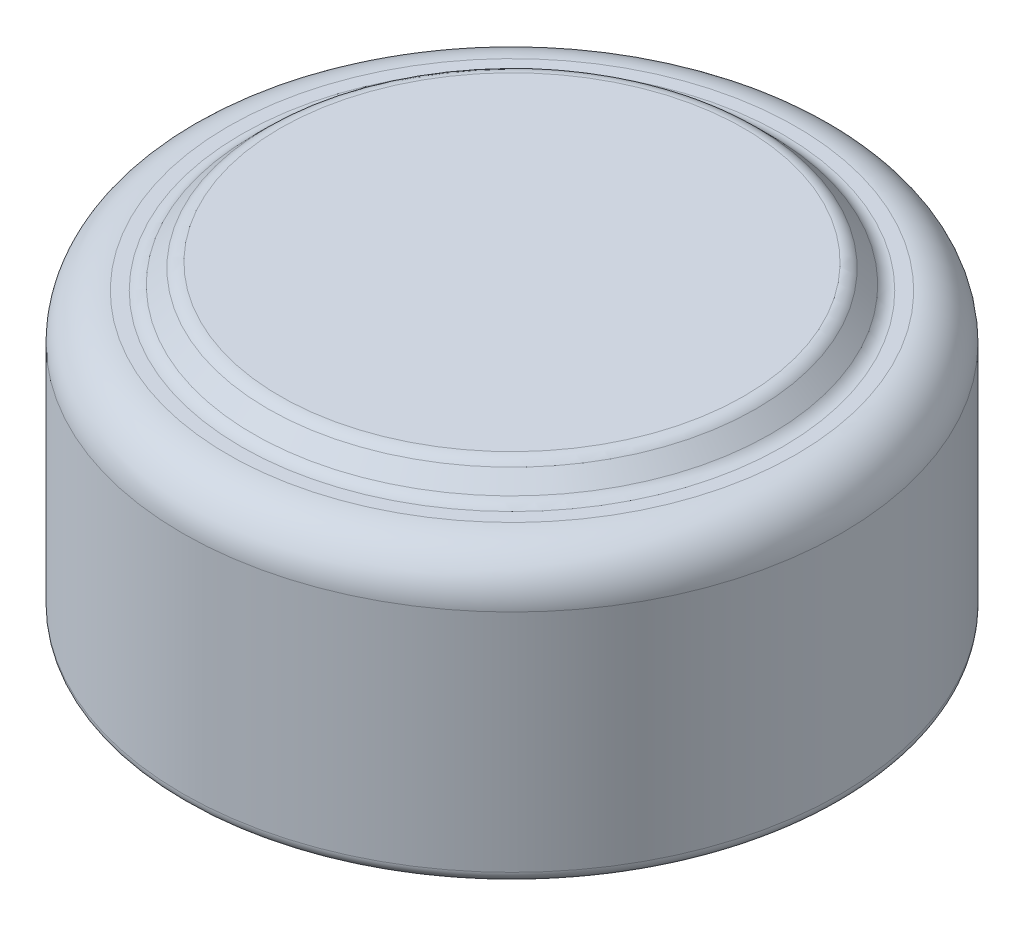
SolidWorks part; units mm, degrees
ref_plane "Front Plane" through (0, 0, 0) normal (0, 0, 1) x (1, 0, 0)
ref_plane "Top Plane" through (0, 0, 0) normal (0, 1, 0) x (1, 0, 0)
ref_plane "Right Plane" through (0, 0, 0) normal (1, 0, 0) x (0, 0, -1)
sketch "Sketch1" plane through (0, 0, 0) normal (0, 0, 1) x (1, 0, 0)
  line L0 (0, 0) -> (-2.8, 0)
  line L1 (-2.9, 0.1) -> (-2.9, 2.084)
  line L2 (-2.0419, 2.7) -> (0, 2.7)
  line L3 (0, 2.7) -> (0, 0)
  line L4 (-2.2761, 2.5279) -> (-2.1479, 2.6561)
  line L7 (-2.3821, 2.484) -> (-2.5, 2.484)
  arc A0 (-2.9, 2.084) -> (-2.5, 2.484) centre (-2.5, 2.084) cw
  arc A1 (-2.0419, 2.7) -> (-2.1479, 2.6561) centre (-2.0419, 2.55) ccw
  arc A2 (-2.3821, 2.484) -> (-2.2761, 2.5279) centre (-2.3821, 2.634) ccw
  arc A3 (-2.8, 0) -> (-2.9, 0.1) centre (-2.8, 0.1) cw
  point P9 (-2.9, 2.484)
  point P13 (-2.32, 2.484)
  point P17 (-2.9, 0)
  point P18 (-2.32, 2.484)
  point P20 (-2.32, 2.484)
  dimension "D6" = 0.4
  dimension "D7" = 0.15
  dimension "D8" = 0.1
  dimension "D1" = 2.9
  dimension "D2" = 2.7
  dimension "D3" = 2.32
  dimension "D4" = 2.484
  dimension "D5" = 45
revolve "Revolve1" add sketch "Sketch1" angle 360 about L3
sketch "Sketch2" plane through (0, 0, 0) normal (0, -1, 0) x (1, 0, 0)
  line L0 (0.25, 0.25) -> (1.4, 0.25)
  line L1 (-0.25, 1.4) -> (0.25, 1.4)
  line L2 (-0.25, 1.4) -> (-0.25, 0.25)
  line L3 (-0.25, -1.4) -> (0.25, -1.4)
  line L4 (0.25, 1.4) -> (0.25, 0.25)
  line L5 (-1.4, 0.25) -> (-0.25, 0.25)
  line L6 (-1.4, 0.25) -> (-1.4, -0.25)
  line L7 (-1.4, -0.25) -> (-0.25, -0.25)
  line L8 (1.4, 0.25) -> (1.4, -0.25)
  line L9 (0.25, -0.25) -> (1.4, -0.25)
  line L10 (0.25, -0.25) -> (0.25, -1.4)
  line L11 (-0.25, -0.25) -> (-0.25, -1.4)
  circle A0 centre (0, 0) radius 1.75 construction
  text T0 "                   SR64" font "Century Gothic" height 0.75
  dimension "D1" = 3.5
  dimension "D2" = 0.25
  dimension "D3" = 0.25
  dimension "D4" = 0.5
  dimension "D5" = 0.5
  dimension "D6" = 2.8
  dimension "D7" = 2.8
  dimension "D8" = 1.4
  dimension "D9" = 1.4
wrap "Wrap1" sketch "Sketch2" wrap type scribe source sketch "Sketch2" face at (-2.8, 0, 0)
